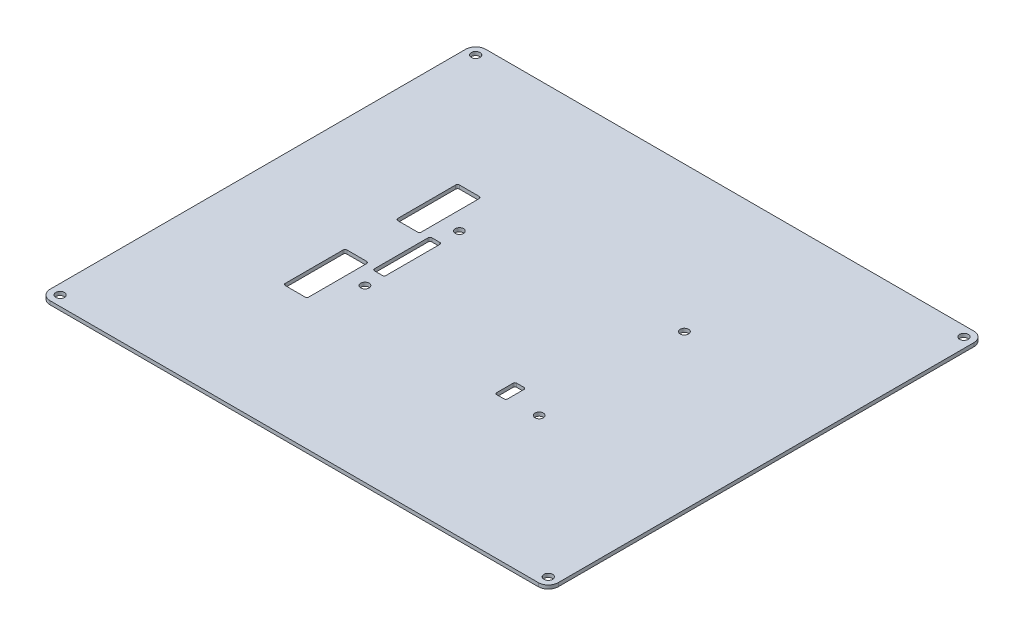
SolidWorks part; units mm, degrees
material "Thornel Mat VMA"
ref_plane "Front Plane" through (0, 0, 0) normal (0, 0, 1) x (1, 0, 0)
ref_plane "Top Plane" through (0, 0, 0) normal (0, 1, 0) x (1, 0, 0)
ref_plane "Right Plane" through (0, 0, 0) normal (1, 0, 0) x (0, 0, -1)
sketch "Sketch1" plane through (0, 0, 0) normal (0, 1, 0) x (1, 0, 0)
  line L0 (70, 0) -> (70, -120) construction
  line L1 (0, 0) -> (140, 0)
  line L2 (0, 0) -> (0, -120)
  line L3 (0, -120) -> (140, -120)
  line L4 (140, 0) -> (140, -120)
  line L5 (2.75, -2.75) -> (0, -2.75) construction
  line L6 (0, -60) -> (140, -60) construction
  line L7 (42.5, -47) -> (97.5, -40) construction
  line L8 (2.75, 0) -> (2.75, -2.75) construction
  line L10 (97.5, -40) -> (97.5, -80) construction
  line L11 (42.5, -47) -> (42.5, -73) construction
  circle A0 centre (2.75, -2.75) radius 1.2
  circle A1 centre (137.25, -2.75) radius 1.2
  circle A2 centre (137.25, -117.25) radius 1.2
  circle A3 centre (2.75, -117.25) radius 1.2
  circle A4 centre (42.5, -47) radius 1.15
  circle A5 centre (97.5, -40) radius 1.15
  circle A6 centre (42.5, -73) radius 1.15
  circle A7 centre (97.5, -80) radius 1.15
  point P27 (70, -43.5)
  point P28 (97.5, -60)
  point P29 (42.5, -60)
  dimension "D3" = 2.4
  dimension "D4" = 2.75
  dimension "D5" = 2.3
  dimension "D1" = 140
  dimension "D2" = 120
  dimension "D6" = 55
  dimension "D7" = 26
  dimension "D8" = 40
extrude "Boss-Extrude1" add sketch "Sketch1" along normal blind 1
fillet "Fillet1" radius 2.75 4 edges at (0, 0.5, 0) (140, 0.5, 0) (140, 0.5, 120) (0, 0.5, 120)
sketch "Sketch2" plane through (0, 0, 0) normal (0, -1, 0) x (1, 0, 0)
  line L0 (34.25, 53) -> (34.25, 67) construction
  line L1 (31, 36) -> (37.5, 36)
  line L2 (31, 36) -> (31, 53)
  line L3 (31, 53) -> (37.5, 53)
  line L4 (37.5, 36) -> (37.5, 53)
  line L5 (37.5, 67) -> (31, 67)
  line L6 (37.5, 67) -> (37.5, 84)
  line L7 (37.5, 84) -> (31, 84)
  line L8 (31, 67) -> (31, 84)
  line L9 (39.8, 52.4) -> (43, 52.4)
  line L10 (39.8, 52.4) -> (39.8, 68.2)
  line L11 (39.8, 68.2) -> (43, 68.2)
  line L12 (43, 52.4) -> (43, 68.2)
  line L13 (86.2, 75.4) -> (89.2, 75.4)
  line L14 (86.2, 75.4) -> (86.2, 80.9)
  line L15 (86.2, 80.9) -> (89.2, 80.9)
  line L16 (89.2, 75.4) -> (89.2, 80.9)
  line L17 (34.25, 60) -> (0, 60) construction
  line L18 (0, 2.75) -> (0, 117.25) construction
  line L19 (137.25, 0) -> (2.75, 0) construction
  line L20 (2.75, 120) -> (137.25, 120) construction
  point P26 (87.7, 75.4)
  dimension "D1" = 31
  dimension "D2" = 37.5
  dimension "D3" = 36
  dimension "D4" = 53
  dimension "D5" = 39.8
  dimension "D6" = 43
  dimension "D7" = 52.4
  dimension "D8" = 51.8
  dimension "D9" = 86.2
  dimension "D10" = 89.2
  dimension "D11" = 75.4
  dimension "D12" = 80.9
extrude "Cut-Extrude1" cut sketch "Sketch2" against normal blind 10
fillet "Fillet2" radius 0.5 16 edges at (86.2, 0.5, 75.4) (89.2, 0.5, 75.4) (86.2, 0.5, 80.9) (89.2, 0.5, 80.9) (31, 0.5, 84) (37.5, 0.5, 84) (31, 0.5, 67) (37.5, 0.5, 67) (43, 0.5, 52.4) (39.8, 0.5, 68.2) (39.8, 0.5, 52.4) (43, 0.5, 68.2) (37.5, 0.5, 53) (37.5, 0.5, 36) (31, 0.5, 53) (31, 0.5, 36)
